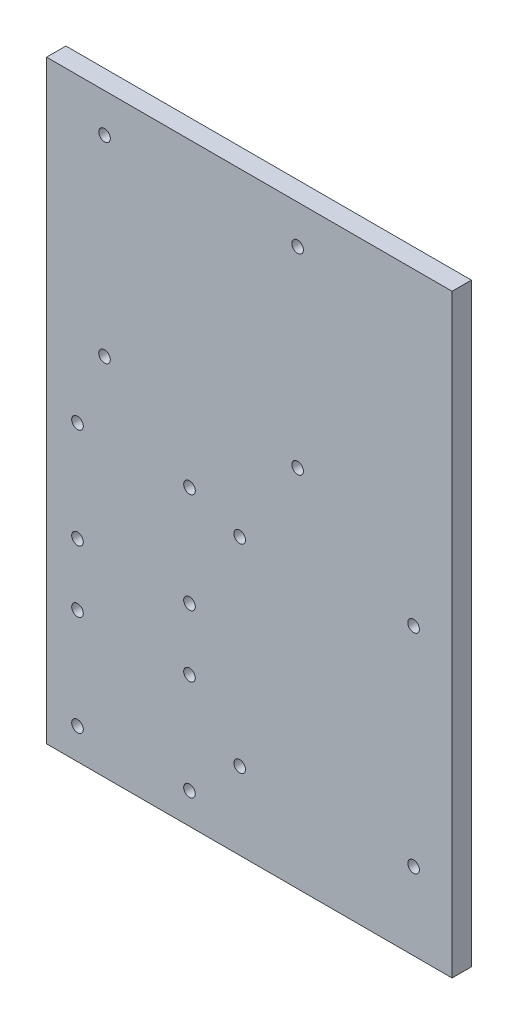
SolidWorks part; units mm, degrees
ref_plane "Front Plane" through (0, 0, 0) normal (0, 0, 1) x (1, 0, 0)
ref_plane "Top Plane" through (0, 0, 0) normal (0, 1, 0) x (1, 0, 0)
ref_plane "Right Plane" through (0, 0, 0) normal (1, 0, 0) x (0, 0, -1)
sketch "Sketch1" plane through (0, 0, 0) normal (0, 0, 1) x (1, 0, 0)
  line L1 (-40, 35) -> (65, 35)
  line L2 (-40, 35) -> (-40, -119)
  line L3 (-40, -119) -> (65, -119)
  line L4 (65, 35) -> (65, -119)
  dimension "D1" = 105
  dimension "D2" = 154
extrude "Boss-Extrude1" add sketch "Sketch1" along normal blind 5 contours L2 L1 L4 L3
sketch "Sketch3" plane through (0, 0, 0) normal (0, 0, -1) x (-1, 0, 0)
  line L1 (40, 35) -> (40, -119) construction
  line L2 (40, -119) -> (-65, -119) construction
  circle A0 centre (32, -43) radius 1.5
  circle A2 centre (32, -85) radius 1.5
  circle A3 centre (3, -111) radius 1.5
  circle A6 centre (3, -43) radius 1.5
  circle A7 centre (32, -111) radius 1.5
  circle A8 centre (3, -85) radius 1.5
  circle A9 centre (3, -69) radius 1.5
  circle A11 centre (32, -69) radius 1.5
  dimension "D1" = 3
  dimension "D2" = 29
  dimension "D3" = 3
  dimension "D4" = 3
  dimension "D6" = 3
  dimension "D7" = 3
  dimension "D8" = 76
  dimension "D9" = 3
  dimension "D10" = 3
  dimension "D11" = 26
  dimension "D12" = 8
  dimension "D13" = 29
  dimension "D14" = 26
  dimension "D15" = 29
  dimension "D16" = 3
  dimension "D17" = 29
  dimension "D5" = 8
  dimension "8" = 8
extrude "Cut-Extrude1" cut sketch "Sketch3" against normal blind 10 contours A0 | A6 | A9 | A2 | A7 | A3 | A8 | A11 region at (-32, -43, 0) region at (-32, -85, 0) region at (-3, -111, 0) region at (-3, -43, 0) region at (-32, -111, 0) region at (-3, -85, 0) region at (-3, -69, 0)
sketch "Sketch4" plane through (0, 0, 0) normal (0, 0, -1) x (-1, 0, 0)
  circle A0 centre (-25, 25) radius 1.5
  circle A1 centre (25, 25) radius 1.5
  circle A2 centre (25, -24.6067) radius 1.5
  circle A3 centre (-25, -24.6067) radius 1.5
extrude "Cut-Extrude2" cut sketch "Sketch4" against normal through all
sketch "Sketch5" plane through (0, 0, 0) normal (0, 0, 1) x (1, 0, 0)
  line L0 (-40, 35) -> (65, 35) construction
  circle A0 centre (12, 1) radius 4
  circle A1 centre (25, 25) radius 1.5 construction
  dimension "D1" = 8
  dimension "D2" = 34
  dimension "D3" = 13
extrude "Cut-Extrude3" [suppressed] cut sketch "Sketch5" along normal through all
sketch "Sketch6" plane through (0, 0, 0) normal (0, 0, -1) x (-1, 0, 0)
  line L0 (40, -119) -> (-65, -119) construction
  line L1 (-55.0184, -45.02) -> (-10, -47.56) construction
  line L2 (-55.0184, -45.02) -> (-55.0184, -99) construction
  line L3 (-55.0184, -99) -> (-10, -99) construction
  line L4 (-10, -47.56) -> (-10, -99) construction
  line L6 (40, 100) -> (40, -100) construction
  circle A0 centre (-10, -47.56) radius 1.5
  circle A1 centre (-55.0184, -45.02) radius 1.5
  circle A2 centre (-55.0184, -99) radius 1.5
  circle A3 centre (-10, -99) radius 1.5
  point P10 (-32.5092, -99)
  point P12 (0, 0)
  point P13 (0, 0)
  point P14 (31.6835, -187.5842)
  point P15 (0, 0)
  point P16 (0, 0)
  point P17 (-16.4203, -193.1971)
  point P18 (-73.2925, -30.0345)
  point P19 (-17.4364, -192.558)
  point P20 (0, 0)
  point P21 (0, 0)
  point P22 (29.8702, -195.3793)
  point P23 (32.7697, -194.6141)
  dimension "D4" = 3
  dimension "D6" = 51.44
  dimension "D1" = 53.98
  dimension "D2" = 45.09
  dimension "D3" = 50
  dimension "D5" = 20
extrude "Cut-Extrude4" cut sketch "Sketch6" against normal through all
